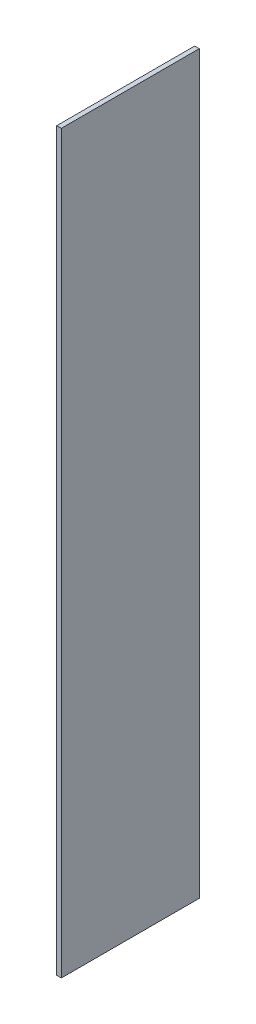
SolidWorks part; units mm, degrees
ref_plane "Front Plane" through (0, 0, 0) normal (0, 0, 1) x (1, 0, 0)
ref_plane "Top Plane" through (0, 0, 0) normal (0, 1, 0) x (1, 0, 0)
ref_plane "Right Plane" through (0, 0, 0) normal (1, 0, 0) x (0, 0, -1)
sketch "Sketch1" plane through (0, 0, 0) normal (0, 0, 1) x (1, 0, 0)
  line L1 (0, 0) -> (0.1, 0)
  line L2 (0, 0) -> (0, 16)
  line L3 (0, 16) -> (0.1, 16)
  line L4 (0.1, 0) -> (0.1, 16)
  dimension "D1" = 16
  dimension "D2" = 0.1
extrude "Boss-Extrude1" add sketch "Sketch1" along normal blind 3
equation "\"A.L\"= 0.06m"
equation "\"A.h\"= 0.005m"
equation "\"A.d\"= 0.003m"
equation "\"A.delta\"= 45.0001"
equation "\"A.w\"= 0.02m"
equation "\"A.v\"= 0.03m"
equation "\"A.s\"= 0.0075m"
equation "\"A.t\"= 0.005m"
equation "\"B.L\"= 0.04m"
equation "\"B.h\"= 0.004m"
equation "\"B.s\"= 0.008m"
equation "\"B.t\"= 0.004m"
equation "\"C.h\"= 0.0062m"
equation "\"C.d\"= 0.003m"
equation "\"C.L\"= 0.05m"
equation "\"C.wmax\"= 0.005m"
equation "\"D.L\"= 0.045m"
equation "\"D.h\"= 0.004m"
equation "\"D.s\"= 0.01m"
equation "\"D.t\"= 0.004m"
equation "\"a_h\"= 0.0001m"
equation "\"a_d\"= 0.003m"
equation "\"a_L\"= 0.01m"
equation "\"b_h\"= 0.0004m"
equation "\"b_d\"= 0.003m"
equation "\"b_L\"= 0.01m"
equation "\"c_h\"= 0.0001m"
equation "\"c_d\"= 0.003m"
equation "\"c_L\"= 0.01m"
equation "\"d_h\"= 0.0001m"
equation "\"d_d\"= 0.003m"
equation "\"d_L\"= 0.01m"
equation "\"S.h\"= 0.015m"
equation "\"S.L\"= 0.0559m"
equation "\"D1@Sketch1\"=\"d_L\"+0.006"
equation "\"D2@Sketch1\"=\"d_h\""
equation "\"D1@Boss-Extrude1\"=\"d_d\""
